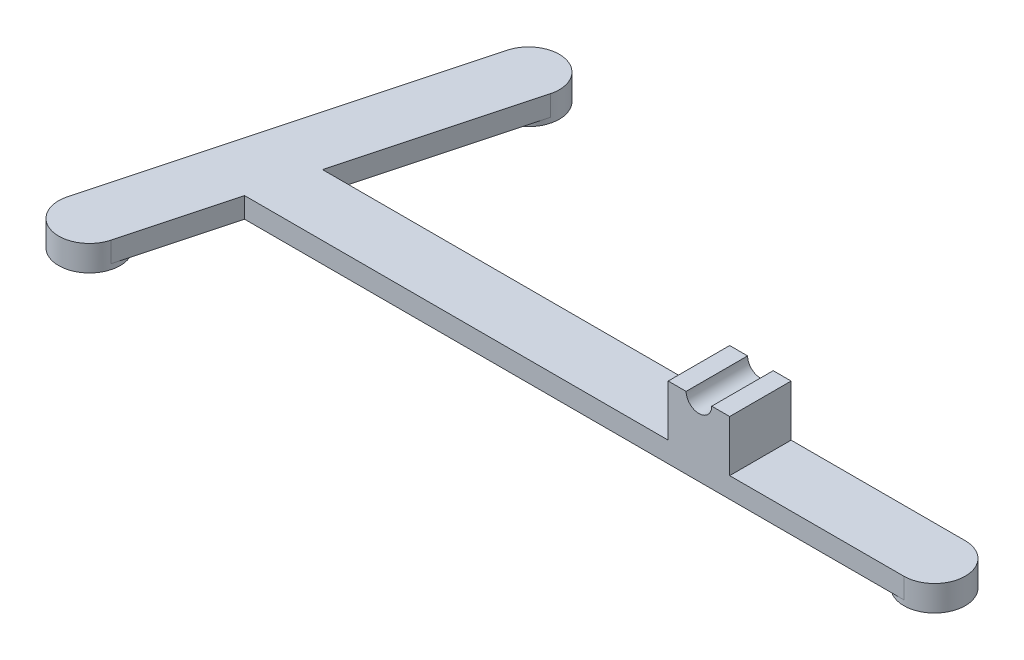
SolidWorks part; units mm, degrees
material "prostheticfoot"
ref_plane "Front Plane" through (0, 0, 0) normal (0, 0, 1) x (1, 0, 0)
ref_plane "Top Plane" through (0, 0, 0) normal (0, 1, 0) x (1, 0, 0)
ref_plane "Right Plane" through (0, 0, 0) normal (1, 0, 0) x (0, 0, -1)
sketch "Sketch2" plane through (0, 0, 0) normal (0, 1, 0) x (1, 0, 0)
  line L0 (-0.8805, -15.5614) -> (17.2369, 52.0534) construction
  line L1 (-6.676, -14.0085) -> (11.4413, 53.6063)
  line L2 (4.9151, -17.1143) -> (23.0324, 50.5005)
  line L3 (5.8183, 9.4386) -> (139.1195, 9.4386) construction
  line L4 (5.8183, 15.4386) -> (139.1195, 15.4386)
  line L5 (5.8183, 3.4386) -> (139.1195, 3.4386)
  line L6 (139.1195, 9.4386) -> (99.1195, 9.4386) construction
  line L8 (93.1195, 3.4386) -> (105.1195, 3.4386)
  line L9 (93.1195, 3.4386) -> (93.1195, 15.4386)
  line L10 (93.1195, 15.4386) -> (105.1195, 15.4386)
  line L11 (105.1195, 3.4386) -> (105.1195, 15.4386)
  line L12 (93.1195, 3.4386) -> (105.1195, 15.4386) construction
  line L13 (93.1195, 15.4386) -> (105.1195, 3.4386) construction
  arc A0 (-6.676, -14.0085) -> (4.9151, -17.1143) centre (-0.8805, -15.5614) ccw
  arc A1 (23.0324, 50.5005) -> (11.4413, 53.6063) centre (17.2369, 52.0534) ccw
  arc A2 (5.8183, 15.4386) -> (5.8183, 3.4386) centre (5.8183, 9.4386) ccw
  arc A3 (139.1195, 3.4386) -> (139.1195, 15.4386) centre (139.1195, 9.4386) ccw
  circle A4 centre (17.2369, 52.0534) radius 6
  circle A5 centre (139.1195, 9.4386) radius 6
  circle A6 centre (-0.8805, -15.5614) radius 6
  point P2 (8.1782, 18.246)
  point P9 (72.4689, 9.4386)
  dimension "D1" = 12
  dimension "D2" = 12
  dimension "D3" = 70
  dimension "D4" = 75
  dimension "D5" = 25
  dimension "D6" = 140
  dimension "D7" = 40
  dimension "D8" = 12
extrude "Boss-Extrude3" add sketch "Sketch2" along normal blind 4 contours L4 A2 L5 L2 | A4 L1 A2 L4 L2 | L5 L9 L4 L2 | A6 L2 L5 A2 L1 | A5 L4 L11 L5 region at (2.3173, 0, 3.2181) region at (11.5339, 0, -31.3368) region at (6.5252, 0, -9.7329) region at (52.5694, 0, -9.3989) region at (119.794, 0, -9.4386)
extrude "Boss-Extrude4" add sketch "Sketch2<5>" along normal blind 4 and the other way blind 1 contours A0 A6 | A1 A4 | A3 A5 region at (-0.8805, 0, 15.5614) region at (17.2369, 0, -52.0534) region at (139.1195, 0, -9.4386)
sketch "Sketch2<5>" plane through (0, 0, 0) normal (0, 1, 0) x (1, 0, 0) same geometry as "Sketch2"
extrude "Boss-Extrude5" add sketch "Sketch2<6>" along normal blind 14 contours L5 L11 L4 L9 region at (99.1195, 0, -9.4386)
sketch "Sketch2<6>" plane through (0, 0, 0) normal (0, 1, 0) x (1, 0, 0) same geometry as "Sketch2"
sketch "Sketch3" plane through (0, 0, -3.4386) normal (0, 0, 1) x (1, 0, 0)
  line L0 (93.1195, 14) -> (105.1195, 14) construction
  circle A0 centre (99.1195, 14) radius 2.5
  dimension "D1" = 5
extrude "Cut-Extrude1" cut sketch "Sketch3" against normal blind 14
